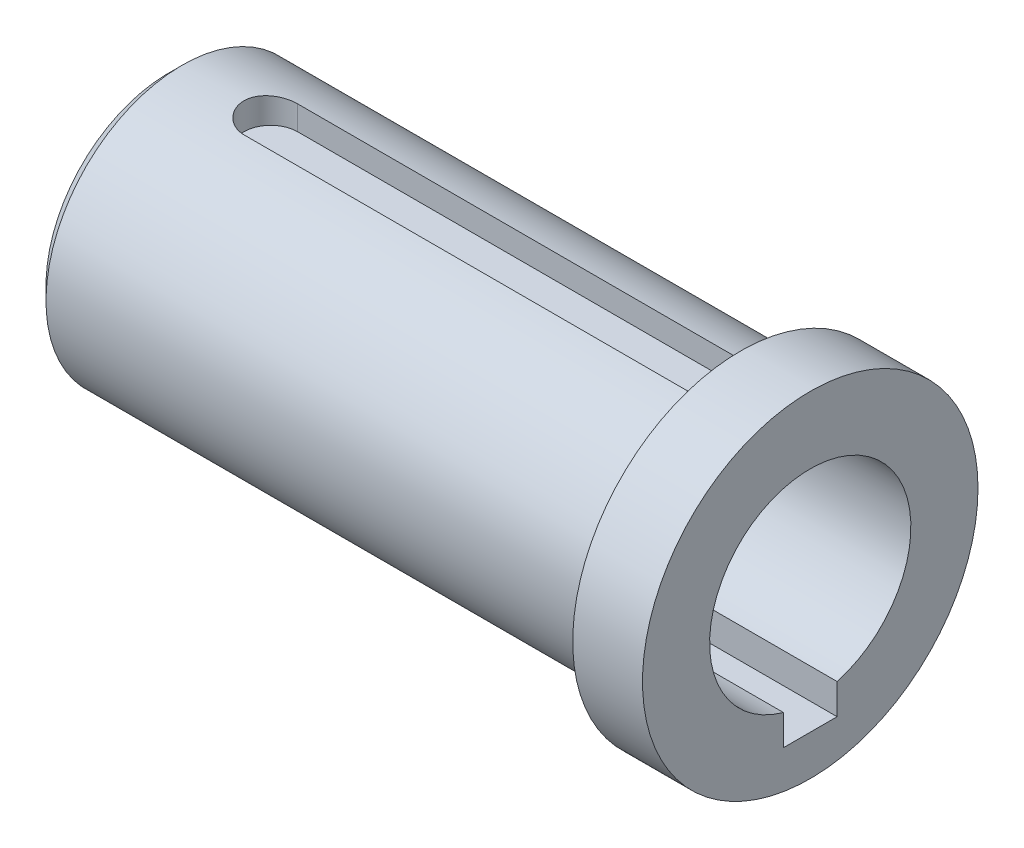
SolidWorks part; units mm, degrees
ref_plane "Front Plane" through (0, 0, 0) normal (0, 0, 1) x (1, 0, 0)
ref_plane "Top Plane" through (0, 0, 0) normal (0, 1, 0) x (1, 0, 0)
ref_plane "Right Plane" through (0, 0, 0) normal (1, 0, 0) x (0, 0, -1)
sketch "Sketch1" plane through (0, 0, 0) normal (1, 0, 0) x (0, 0, -1)
  circle A0 centre (0, 0) radius 10.15
  circle A1 centre (0, 0) radius 7.5
  dimension "D1" = 20.3
  dimension "D2" = 15
extrude "Boss-Extrude1" add sketch "Sketch1" along normal blind 47.8
sketch "Sketch2" plane through (47.8, 0, 0) normal (1, 0, 0) x (0, 0, -1)
  circle A0 centre (0, 0) radius 12.5
  circle A1 centre (0, 0) radius 10.15 construction
  circle A2 centre (0, 0) radius 10.15
  dimension "D1" = 25
extrude "Boss-Extrude2" add sketch "Sketch2" against normal blind 5.2
sketch "Sketch5" plane through (0, 0, 0) normal (-1, 0, 0) x (0, 0, 1)
  line L0 (-2, -9.5) -> (-2, -5.5)
  line L1 (-2, -9.5) -> (2, -9.5)
  line L2 (-2, -5.5) -> (2, -5.5)
  line L3 (2, -9.5) -> (2, -5.5)
  line L4 (-2, -9.5) -> (2, -5.5) construction
  line L5 (-2, -5.5) -> (2, -9.5) construction
  line L6 (0, 0) -> (0, -7.5) construction
  circle A0 centre (0, 0) radius 7.5 construction
  point P1 (0, -7.5)
  dimension "D1" = 4
extrude "Cut-Extrude2" cut sketch "Sketch5" against normal through all
sketch "Sketch6" plane through (0, 0, 0) normal (-1, 0, 0) x (0, 0, 1)
  line L0 (-2, 12.15) -> (-2, 8.15)
  line L1 (-2, 12.15) -> (2, 12.15)
  line L2 (-2, 8.15) -> (2, 8.15)
  line L3 (2, 12.15) -> (2, 8.15)
  line L4 (-2, 12.15) -> (2, 8.15) construction
  line L5 (-2, 8.15) -> (2, 12.15) construction
  line L6 (-2, -9.5) -> (2, -9.5) construction
  line L7 (0, 0) -> (0, 10.15) construction
  circle A0 centre (0, 0) radius 10.15 construction
  point P1 (0, 10.15)
extrude "Cut-Extrude3" cut sketch "Sketch6" against normal blind 20 from offset 10 offset against normal yes
sketch "Sketch4" plane through (0, 0, 0) normal (0, 1, 0) x (1, 0, 0)
  line L0 (7.6, 0) -> (40.6, 0) construction
  line L1 (7.6, 2) -> (40.6, 2)
  line L2 (7.6, -2) -> (40.6, -2)
  line L3 (42.6, 12.5) -> (42.6, -12.5) construction
  arc A0 (7.6, 2) -> (7.6, -2) centre (7.6, 0) ccw
  arc A1 (40.6, -2) -> (40.6, 2) centre (40.6, 0) ccw
  point P2 (24.1, 0)
  dimension "D1" = 33
  dimension "D2" = 4
extrude "Cut-Extrude1" cut sketch "Sketch4" along normal blind 10 from vertex starting at point (30, 8.15, -2)
chamfer "Chamfer1" distance 1 angle 45 1 edges at (0, 0, -10.15)
move or copy body "Body-Move/Copy1" [suppressed] bodies to move or copy 103
